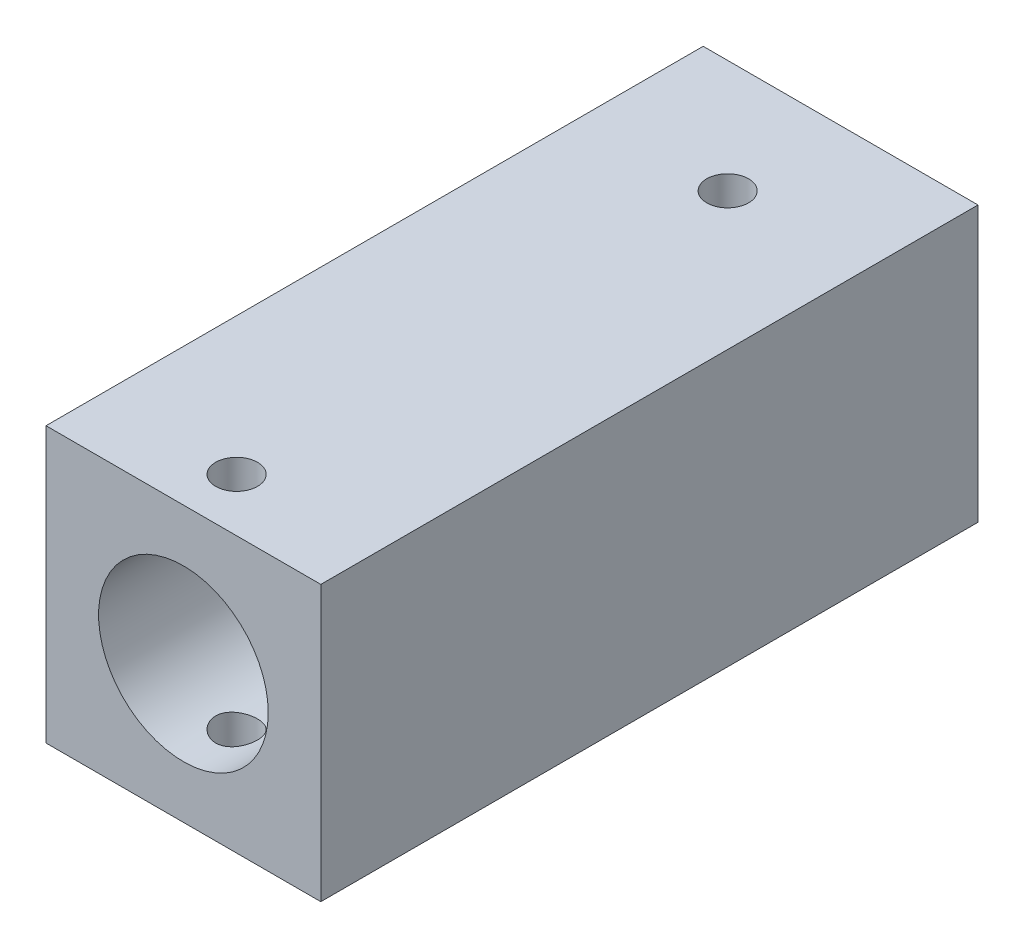
SolidWorks part; units mm, degrees
material "ABS generico"
ref_plane "Piano frontale" through (0, 0, 0) normal (0, 0, 1) x (1, 0, 0)
ref_plane "Piano superiore" through (0, 0, 0) normal (0, 1, 0) x (1, 0, 0)
ref_plane "Piano destro" through (0, 0, 0) normal (1, 0, 0) x (0, 0, -1)
sketch "Schizzo1" plane through (0, 0, 0) normal (0, 0, 1) x (1, 0, 0)
  line L4 (-7.3767, -9.877) -> (-7.3597, -9.8281)
  line L24 (7.9489, 13.813) -> (-15.0511, 13.813)
  line L25 (7.9489, 13.813) -> (7.9489, -9.187)
  line L26 (7.9489, -9.187) -> (-15.0511, -9.187)
  line L27 (-15.0511, 13.813) -> (-15.0511, -9.187)
  dimension "D1" = 23
extrude "Estrusione-Estrusione1" add sketch "Schizzo1" along normal blind 55 contours L24 L27 L26 L25 region at (-3.5511, 2.313, 0)
sketch "Schizzo18" plane through (0, 0, 0) normal (0, 0, -1) x (-1, 0, 0)
  line L0 (-7.9489, 2.313) -> (15.0511, 2.313) construction
  line L1 (-7.9489, 13.813) -> (-7.9489, -9.187) construction
  line L2 (15.0511, 13.813) -> (15.0511, -9.187) construction
  line L3 (3.5511, 13.813) -> (3.5511, -9.187) construction
  line L4 (-7.9489, 13.813) -> (15.0511, 13.813) construction
  line L5 (-7.9489, -9.187) -> (15.0511, -9.187) construction
  circle A0 centre (3.5511, 2.313) radius 7.1
  dimension "D1" = 14.2
extrude "Taglio-Estrusione12" cut sketch "Schizzo18" against normal up to next
chamfer "Smusso4" distance 1 distance2 3 1 edges at (-10.6511, 2.313, 0) first distance on face at (-10.6511, 2.313, 0)
sketch "Schizzo19" plane through (0, 13.813, 0) normal (0, 1, 0) x (1, 0, 0)
  line L0 (-3.5511, -55) -> (-3.5511, 0) construction
  line L1 (7.9489, -55) -> (-15.0511, -55) construction
  line L2 (7.9489, 0) -> (-15.0511, 0) construction
  circle A0 centre (-3.5511, -50.55) radius 1.75
  circle A1 centre (-3.5511, -9.45) radius 1.75
  dimension "D3" = 3.5
  dimension "D4" = 3.5
  dimension "D1" = 41.1
  dimension "D2" = 4.45
extrude "Taglio-Estrusione13" cut sketch "Schizzo19" against normal through all
